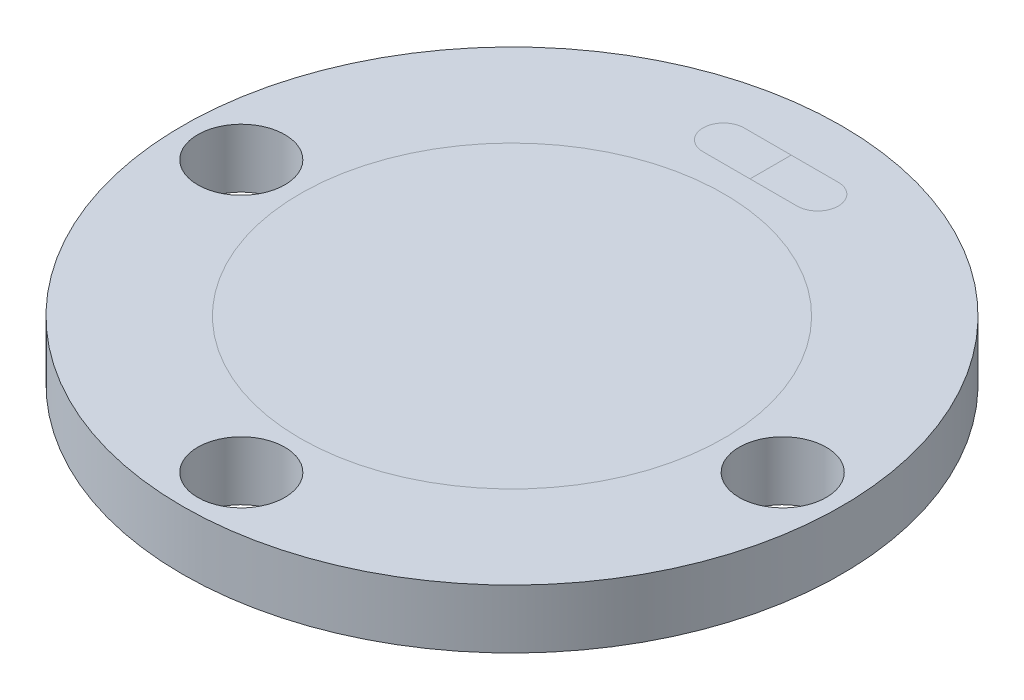
SolidWorks part; units mm, degrees
ref_plane "前视基准面" through (0, 0, 0) normal (0, 0, 1) x (1, 0, 0)
ref_plane "上视基准面" through (0, 0, 0) normal (0, 1, 0) x (1, 0, 0)
ref_plane "右视基准面" through (0, 0, 0) normal (1, 0, 0) x (0, 0, -1)
other "Configuration Table"
sketch "草图1" plane through (0, 0, 0) normal (0, 1, 0) x (1, 0, 0)
  circle A0 centre (0, 0) radius 28
extrude "凸台-拉伸1" add sketch "草图1" along normal blind 3
sketch "草图2" plane through (0, 3, 0) normal (0, 1, 0) x (1, 0, 0)
  circle A0 centre (0, 0) radius 18
split line "分割线1"
sketch "草图5" plane through (0, 3, 0) normal (0, 1, 0) x (1, 0, 0)
  line L1 (4.0218, 21.9524) -> (-3.9782, 21.9524) construction
  line L2 (4.0218, 20.2024) -> (-3.9782, 20.2024)
  line L3 (4.0218, 23.7024) -> (-3.9782, 23.7024)
  arc A1 (4.0218, 20.2024) -> (4.0218, 23.7024) centre (4.0218, 21.9524) ccw
  arc A2 (-3.9782, 23.7024) -> (-3.9782, 20.2024) centre (-3.9782, 21.9524) ccw
  point P7 (0.0218, 21.9524)
split line "分割线2"
sketch "草图6" plane through (0, 3, 0) normal (0, 1, 0) x (1, 0, 0)
  line L0 (0.0218, 23.7024) -> (0.0218, 20.2024)
  line L1 (-3.9782, 23.7024) -> (4.0218, 23.7024) construction
  line L2 (4.0218, 20.2024) -> (-3.9782, 20.2024) construction
split line "分割线3"
sketch "草图7" plane through (0, 3, 0) normal (0, 1, 0) x (1, 0, 0)
  circle A0 centre (23, 0) radius 3.7
extrude "切除-拉伸1" cut sketch "草图7" against normal blind 10
sketch "草图8" plane through (0, 3, 0) normal (0, 1, 0) x (1, 0, 0)
  circle A0 centre (-23, 0) radius 3.7
extrude "切除-拉伸2" cut sketch "草图8" against normal blind 10
sketch "草图9" plane through (0, 3, 0) normal (0, 1, 0) x (1, 0, 0)
  circle A0 centre (0, -23) radius 3.7
extrude "切除-拉伸3" cut sketch "草图9" against normal blind 10
extrude "凸台-拉伸3" add sketch "草图1<3>" against normal blind 2
sketch "草图1<3>" plane through (0, 0, 0) normal (0, 1, 0) x (1, 0, 0) same geometry as "草图1"
extrude "切除-拉伸4" cut sketch "草图9<2>" against normal blind 5
sketch "草图9<2>" plane through (0, 3, 0) normal (0, 1, 0) x (1, 0, 0) same geometry as "草图9"
extrude "切除-拉伸5" cut sketch "草图8<2>" against normal blind 5
sketch "草图8<2>" plane through (0, 3, 0) normal (0, 1, 0) x (1, 0, 0) same geometry as "草图8"
extrude "切除-拉伸6" cut sketch "草图7<2>" against normal blind 5
sketch "草图7<2>" plane through (0, 3, 0) normal (0, 1, 0) x (1, 0, 0) same geometry as "草图7"
